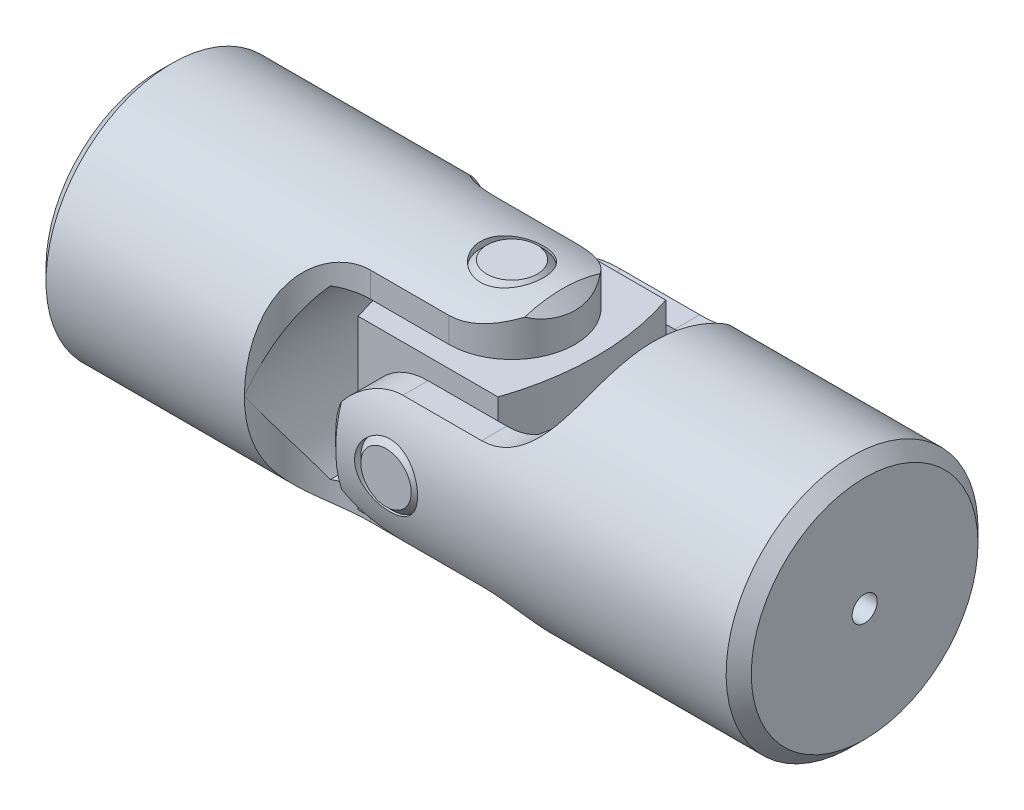
SolidWorks part; units mm, degrees
ref_plane "Front Plane" through (0, 0, 0) normal (0, 0, 1) x (1, 0, 0)
ref_plane "Top Plane" through (0, 0, 0) normal (0, 1, 0) x (1, 0, 0)
ref_plane "Right Plane" through (0, 0, 0) normal (1, 0, 0) x (0, 0, -1)
sketch "Sketch0" plane through (0, 0, 0) normal (0, 1, 0) x (1, 0, 0)
  line L0 (-88.9, 0) -> (88.9, 0) construction
  line L1 (-88.9, 31.75) -> (-88.9, -31.75) construction
  line L2 (-36.5125, 3.175) -> (-36.5125, -3.175) construction
  line L3 (-36.5125, 3.175) -> (-33.3375, 0) construction
  line L4 (-33.3375, 0) -> (-36.5125, -3.175) construction
  line L5 (-34.925, 1.5875) -> (-34.925, -1.5875) construction
  point P7 (-36.5125, 0)
  point P8 (0, 0)
  point P12 (-34.925, 0)
  dimension "D1" = 6.35
sketch "Sketch1" plane through (0, 0, 0) normal (0, 1, 0) x (1, 0, 0)
  line L0 (-88.9, 31.75) -> (-35.7187, 31.75)
  line L1 (15.875, 31.75) -> (15.875, 0)
  line L2 (15.875, 0) -> (-88.9, 0)
  line L3 (-88.9, 0) -> (-88.9, 31.75)
  line L4 (-88.9, 31.75) -> (-88.9, -31.75) construction
  line L5 (-88.9, 0) -> (88.9, 0) construction
  line L6 (-35.7187, 31.75) -> (15.875, 31.75)
  line L7 (-35.7187, 1.5875) -> (-35.7187, 31.75) construction
  line L11 (0, 0) -> (31.75, 0) construction
  line L12 (-34.925, 1.5875) -> (-36.5125, 1.5875) construction
  line L13 (-36.5125, 3.175) -> (-36.5125, -3.175) construction
  circle A0 centre (0, 0) radius 31.75 construction
  dimension "D3" = 104.775
revolve "Revolve1" add sketch "Sketch1" angle 360 about L0
chamfer "Chamfer1" distance 3.175 angle 45 2 edges at (-88.9, 0, 31.75) (15.875, 0, 31.75)
sketch "Sketch2" plane through (0, 0, 0) normal (0, 1, 0) x (1, 0, 0)
  line L0 (-85.725, 31.75) -> (-35.7124, 31.75) construction
  line L1 (-35.7187, 31.75) -> (15.875, 31.75) construction
  line L2 (12.7, 31.75) -> (-85.725, 31.75) construction
  line L4 (-88.9, 0) -> (15.875, 0) construction
  line L5 (-35.7124, 31.75) -> (31.75, 31.75)
  line L6 (31.75, 31.75) -> (31.75, -31.75)
  line L7 (31.75, -31.75) -> (-35.7124, -31.75)
  line L8 (0, 15.875) -> (0, 0) construction
  line L9 (0, 15.875) -> (-19.8374, 15.875)
  line L10 (-35.7124, 31.75) -> (-35.7124, -31.75) construction
  line L11 (0, -15.875) -> (-19.8374, -15.875)
  arc A0 (-35.7124, 31.75) -> (-19.8374, 15.875) centre (-19.8374, 31.75) ccw
  arc A1 (0, -15.875) -> (0, 15.875) centre (0, 0) ccw
  arc A2 (-19.8374, -15.875) -> (-35.7124, -31.75) centre (-19.8374, -31.75) ccw
  dimension "D1" = 31.75
  dimension "D" = 53.1876
extrude "Extrude1" cut sketch "Sketch2" against normal through all and the other way through all
sketch "Sketch3" plane through (0, 0, 0) normal (0, 0, 1) x (1, 0, 0)
  line L0 (-27.7749, 21.1455) -> (-35.7124, 13.208) construction
  line L1 (-27.7749, 21.1455) -> (31.75, 21.1455)
  line L2 (-35.7124, 13.208) -> (-35.7124, -13.208) construction
  line L3 (-27.7749, -21.1455) -> (31.75, -21.1455)
  line L4 (31.75, 21.1455) -> (31.75, -21.1455)
  line L5 (-35.7124, -13.208) -> (-27.7749, -21.1455) construction
  line L6 (-35.7124, 0) -> (-19.8374, 0) construction
  line L7 (-19.8374, -27.4963) -> (-19.8374, 27.4963) construction
  line L8 (31.75, 0) -> (-35.7124, 0) construction
  line L9 (-27.7749, 0) -> (-27.7749, 21.1455) construction
  arc A0 (-27.7749, 21.1455) -> (-27.7749, -21.1455) centre (-3.5778, 0) ccw
  dimension "D1" = 42.291
extrude "Extrude3" cut sketch "Sketch3" against normal through all and the other way through all
sketch "Sketch4" plane through (-88.9, 0, 0) normal (-1, 0, 0) x (0, 0, 1)
  circle A0 centre (0, 0) radius 3.175
  circle A1 centre (0, 0) radius 19.05 construction
  dimension "Max Bore Dia" = 38.1
extrude "Extrude4" cut sketch "Sketch4" against normal blind 6.35
sketch "Sketch5" plane through (-82.55, 0, 0) normal (-1, 0, 0) x (0, 0, 1)
  circle A0 centre (0, 0) radius 3.175 construction
  circle A1 centre (0, 0) radius 3.175
extrude "Extrude5" cut sketch "Sketch5" against normal through all draft 45
sketch "Sketch6" plane through (0, 0, 0) normal (0, 1, 0) x (1, 0, 0)
  line L0 (-88.9, 0) -> (88.9, 0) construction
  line L1 (15.875, 0) -> (7.9375, 0) construction
  line L2 (7.9375, 0) -> (0, 0) construction
  circle A0 centre (0, 0) radius 7.9375
  arc A1 (0, -15.875) -> (0, 15.875) centre (0, 0) ccw construction
  dimension "D1" = 15.875
extrude "Extrude6" cut sketch "Sketch6" against normal through all and the other way through all
mirror "Mirror1" about plane through (0, 0, 0) normal (1, 0, 0) of bodies 109 122
move or copy body "Body-Move/Copy1" bodies to move or copy 110 copy no rotation origin (0, 0, 0) rotation axis (1, 0, 0) rotation angle 90
sketch "Sketch18" plane through (0, 0, 0) normal (0, 1, 0) x (1, 0, 0)
  line L8 (0, 0) -> (88.9, 0) construction
  line L10 (-36.5125, 3.175) -> (-88.9, 3.175)
  line L12 (-36.5125, 3.175) -> (-36.5125, -3.175)
  line L13 (-36.5125, -3.175) -> (-88.9, -3.175)
  line L14 (-88.9, 31.75) -> (-88.9, -31.75) construction
  line L15 (0, 0) -> (0, 21.9558) construction
  line L16 (36.5125, -3.175) -> (88.9, -3.175)
  line L17 (36.5125, 3.175) -> (36.5125, -3.175)
  line L18 (36.5125, 3.175) -> (88.9, 3.175)
sketch "Sketch10" plane through (0, 0, 0) normal (0, 0, 1) x (1, 0, 0)
  line L0 (-21.1455, 21.1455) -> (21.1455, -21.1455) construction
  line L1 (-21.1455, 21.1455) -> (21.1455, 21.1455)
  line L2 (-21.1455, 21.1455) -> (-21.1455, -21.1455)
  line L3 (-21.1455, -21.1455) -> (21.1455, -21.1455)
  line L4 (21.1455, 21.1455) -> (21.1455, -21.1455)
  line L5 (0, 21.1455) -> (15.875, 21.1455) construction
extrude "Extrude10" add sketch "Sketch10" against normal up to surface (21.1455 mm away) and the other way up to surface (21.1455 mm away) separate body up to face at (0, 7.9375, -21.1455) other way up to face at (0, -7.9375, 21.1455)
sketch "Sketch20" plane through (0, 21.1455, 0) normal (0, 1, 0) x (1, 0, 0)
  line L4 (21.1455, 21.1455) -> (-21.1455, 21.1455) construction
  line L5 (21.1455, -21.1455) -> (-21.1455, -21.1455) construction
  line L6 (-21.1455, 21.1455) -> (-21.1455, -21.1455) construction
  line L7 (21.1455, 21.1455) -> (21.1455, -21.1455) construction
  line L8 (22.1615, -22.1615) -> (22.1615, 22.1615)
  line L9 (22.1615, 22.1615) -> (-22.1615, 22.1615)
  line L10 (-22.1615, 22.1615) -> (-22.1615, -22.1615)
  line L11 (-22.1615, -22.1615) -> (22.1615, -22.1615)
  line L12 (22.1615, -22.1615) -> (22.1615, 22.1615)
  line L13 (22.1615, 22.1615) -> (17.6213, 22.1615)
  line L14 (-22.1615, 22.1615) -> (-22.1615, -22.1615)
  line L15 (-22.1615, -22.1615) -> (-17.6212, -22.1615)
  line L16 (-17.6212, 21.1455) -> (-17.6212, 22.1615)
  line L17 (17.6213, 21.1455) -> (17.6213, 22.1615)
  line L18 (17.6212, -21.1455) -> (17.6212, -22.1615)
  line L19 (-17.6212, -21.1455) -> (-17.6212, -22.1615)
  line L20 (-17.6212, 22.1615) -> (-22.1615, 22.1615)
  line L21 (17.6212, -22.1615) -> (22.1615, -22.1615)
  line L22 (-88.9, 0) -> (15.875, 0) construction
  line L23 (21.1455, 21.1455) -> (-21.1455, 21.1455) construction
  arc A0 (17.6213, 21.1455) -> (17.6212, -21.1455) centre (-44.0531, 0) cw
  arc A1 (-17.6212, 21.1455) -> (-17.6212, -21.1455) centre (44.0531, 0) ccw
  dimension "D2" = 42.291
  dimension "D3" = 3.5242
extrude "Cut-Extrude2" cut sketch "Sketch20" against normal through all
sketch "Sketch13" plane through (0, 0, 0) normal (0, 1, 0) x (1, 0, 0)
  circle A0 centre (0, 0) radius 7.9375 construction
  circle A1 centre (0, 0) radius 7.9375
extrude "Extrude13" cut sketch "Sketch13" against normal through all and the other way through all
sketch "Sketch14" plane through (0, 0, 0) normal (0, 1, 0) x (1, 0, 0)
  circle A1 centre (0, 0) radius 7.9375
  circle A2 centre (0, 0) radius 7.9375
  dimension "D1" = 0
extrude "Extrude14" add sketch "Sketch14" along normal mid plane 63.5 separate body
sketch "Sketch15" plane through (0, 0, 0) normal (0, 0, 1) x (1, 0, 0)
  circle A0 centre (0, 0) radius 7.9375 construction
  circle A1 centre (0, 0) radius 7.9375
extrude "Extrude15" cut sketch "Sketch15" against normal through all and the other way through all
sketch "Sketch16" plane through (0, 0, 0) normal (0, 0, 1) x (1, 0, 0)
  circle A1 centre (0, 0) radius 7.9375
  circle A2 centre (0, 0) radius 7.9375
  dimension "D1" = 0
extrude "Extrude16" add sketch "Sketch16" along normal mid plane 63.5
chamfer "Chamfer3" distance 1.5875 angle 45 4 edges at (0, -31.75, 7.9375) (0, 31.75, 7.9375) (7.9375, 0, 31.75) (7.9375, 0, -31.75)
move or copy body "Body-Move/Copy2" [suppressed] bodies to move or copy 111 copy no rotation origin (0, 0, 0) rotation axis (0, 0, -1) rotation angle 35
equation "\"D2@Sketch3\" = \"D1@Sketch3\" / 4"
equation "\"D1@Extrude14\" = \"OD@Sketch0\""
equation "\"D1@Extrude16\" = \"D1@Extrude14\""
equation "\"D1@Sketch3\" = \"OD@Sketch0\"*.666"
equation "\"D1@Chamfer1\" = \"OD@Sketch0\"/20"
equation "\"D1@Chamfer3\" = \"D1@Chamfer1\"*.50"
equation "\"D3@Sketch20\" = \"D2@Sketch20\"/12"
